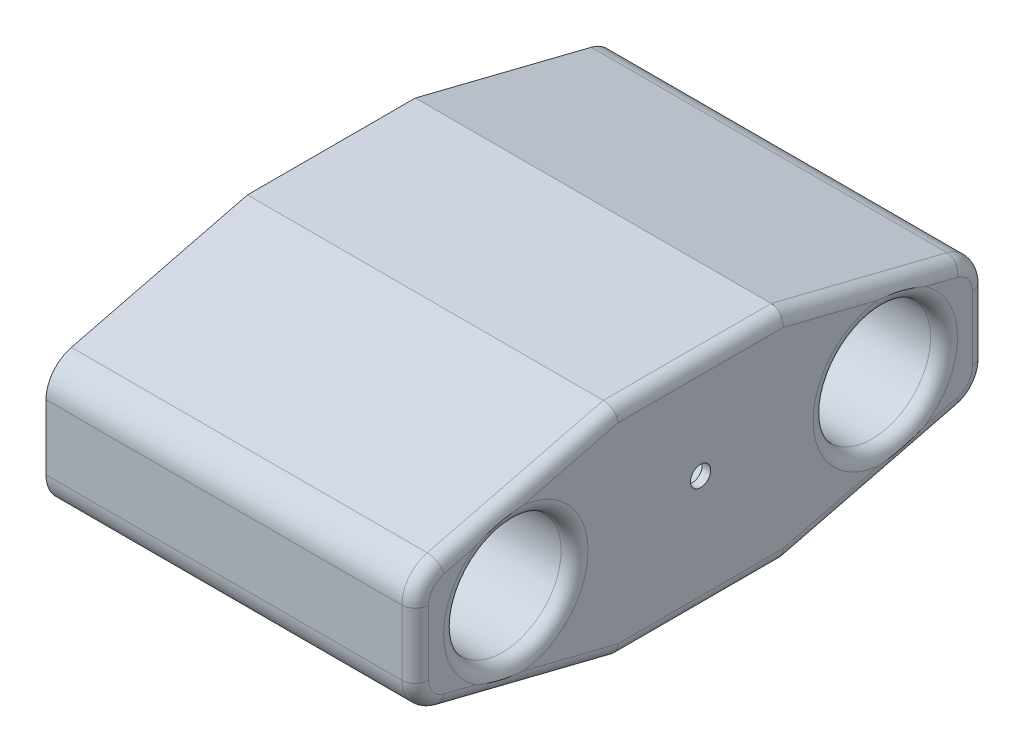
SolidWorks part; units mm, degrees
ref_plane "Front Plane" through (0, 0, 0) normal (0, 0, 1) x (1, 0, 0)
ref_plane "Top Plane" through (0, 0, 0) normal (0, 1, 0) x (1, 0, 0)
ref_plane "Right Plane" through (0, 0, 0) normal (1, 0, 0) x (0, 0, -1)
sketch "Sketch1" plane through (0, 0, 0) normal (1, 0, 0) x (0, 0, -1)
  line L0 (-25, 25) -> (-85, 10)
  line L1 (-25, 25) -> (25, 25)
  line L2 (-85, 10) -> (-85, -25)
  line L3 (-25, -40) -> (25, -40)
  line L4 (85, 10) -> (85, -25)
  line L5 (0, -40) -> (0, 40) construction
  line L6 (-85, 0) -> (85, 0) construction
  line L7 (-25, -40) -> (-85, -25)
  line L8 (25, 25) -> (85, 10)
  line L9 (25, -40) -> (85, -25)
  point P0 (0, 0)
  dimension "D3" = 35
  dimension "D1" = 50
  dimension "D2" = 35
  dimension "D8" = 25
extrude "Boss-Extrude1" add sketch "Sketch1" against normal blind 110
sketch "Sketch2" plane through (0, 0, 0) normal (1, 0, 0) x (0, 0, -1)
  circle A1 centre (-55.0412, -7.5) radius 17.5
  dimension "D3" = 35
extrude "Cut-Extrude1" cut sketch "Sketch2" against normal blind 50
fillet "Fillet1" radius 10 4 edges at (-55, -25, -85) (-55, 10, -85) (-55, -25, 85) (-55, 10, 85)
mirror "Mirror1" about plane through (0, 0, 0) normal (0, 0, 1) of "Cut-Extrude1"
shell "Shell1" thickness 2.5 removed face at (-110, -7.5, 0)
sketch "Sketch4" plane through (-110, 0, 0) normal (-1, 0, 0) x (0, 0, 1)
  line L0 (-24.6922, 23.5) -> (24.6922, 23.5)
  line L1 (-24.6922, 22.5) -> (24.6922, 22.5) construction
  line L3 (83.5, -2.845) -> (83.5, -17.0974)
  line L4 (82.5, 2.1922) -> (82.5, -17.1922) construction
  line L5 (77.1381, -25.416) -> (25.0289, -38.5)
  line L6 (25.0289, -38.5) -> (-24.6922, -38.5)
  line L7 (-24.6922, -38.5) -> (-77.0345, -25.4448)
  line L8 (-24.6922, 23.5) -> (-76.982, 10.4683)
  line L9 (-83.5, -2.8078) -> (-83.5, -17.1686)
  line L10 (-82.5, -17.1922) -> (-82.5, 2.1922) construction
  line L11 (-24.6922, 22.5) -> (24.6922, 22.5)
  line L12 (24.6922, 22.5) -> (76.819, 9.4683)
  line L13 (-24.6922, 22.5) -> (-76.819, 9.4683)
  line L14 (-76.819, -24.4683) -> (-24.6922, -37.5)
  line L15 (-24.6922, -37.5) -> (24.6922, -37.5)
  line L16 (24.6922, -37.5) -> (76.819, -24.4683)
  line L17 (82.5, -17.1922) -> (82.5, 2.1922)
  line L18 (-82.5, 2.1922) -> (-82.5, -17.1922)
  line L19 (-83.5, -2.8078) -> (-83.5, 2.1922)
  line L21 (76.819, 10.4683) -> (24.6922, 23.5)
  line L22 (83.5, -2.845) -> (83.5, 2.1239)
  arc A1 (-77.0345, -25.4448) -> (-83.5, -17.1686) centre (-74.9703, -17.1686) cw
  arc A2 (77.1381, -25.416) -> (83.5, -17.0974) centre (75.0895, -17.2573) ccw
  arc A4 (-76.819, 9.4683) -> (-82.5, 2.1922) centre (-75, 2.1922) ccw
  arc A5 (-82.5, -17.1922) -> (-76.819, -24.4683) centre (-75, -17.1922) ccw
  arc A6 (76.819, -24.4683) -> (82.5, -17.1922) centre (75, -17.1922) ccw
  arc A8 (-76.982, 10.4683) -> (-83.5, 2.1922) centre (-75.2055, 2.3645) ccw
  arc A10 (76.819, 9.4683) -> (82.5, 2.1922) centre (75, 2.1922) cw
  arc A11 (76.819, 10.4683) -> (83.5, 2.1239) centre (74.9485, 2.1239) cw
  dimension "D1" = 1
  dimension "D2" = 1
  dimension "D3" = 1
  dimension "D4" = 1
  dimension "D5" = 1
  dimension "D6" = 1
  dimension "D7" = 1
  dimension "D8" = 1
  dimension "D10" = 1
extrude "Cut-Extrude4" cut sketch "Sketch4" against normal blind 5
fillet "Fillet2" radius 4 14 edges at (0, -40, 0) (0, -33.4468, 51.2127) (0, -23.3464, 82.8821) (0, -7.5, 85) (0, 8.3464, 82.8821) (0, 18.4468, 51.2127) (0, 25, 0) (0, 18.4468, -51.2127) (0, 8.3464, -82.8821) (0, -7.5, -85) (0, -23.3464, -82.8821) (0, -33.4468, -51.2127) (0, -7.5, 37.5412) (0, -7.5, -37.5412)
sketch "Sketch5" plane through (0, 0, 0) normal (1, 0, 0) x (0, 0, -1)
  line L0 (24.5076, 21) -> (-24.5076, 21) construction
  circle A0 centre (0, -5) radius 3
  dimension "D2" = 6
  dimension "D1" = 26
extrude "Cut-Extrude5" cut sketch "Sketch5" against normal blind 20
sketch "Sketch6" plane through (-50, 0, 0) normal (1, 0, 0) x (0, 0, -1)
  circle A0 centre (-55.0412, -7.5) radius 1.5
  dimension "D1" = 3
extrude "Cut-Extrude6" cut sketch "Sketch6" against normal blind 20
mirror "Mirror3" about plane through (0, 0, 0) normal (0, 0, 1) of "Cut-Extrude6"
